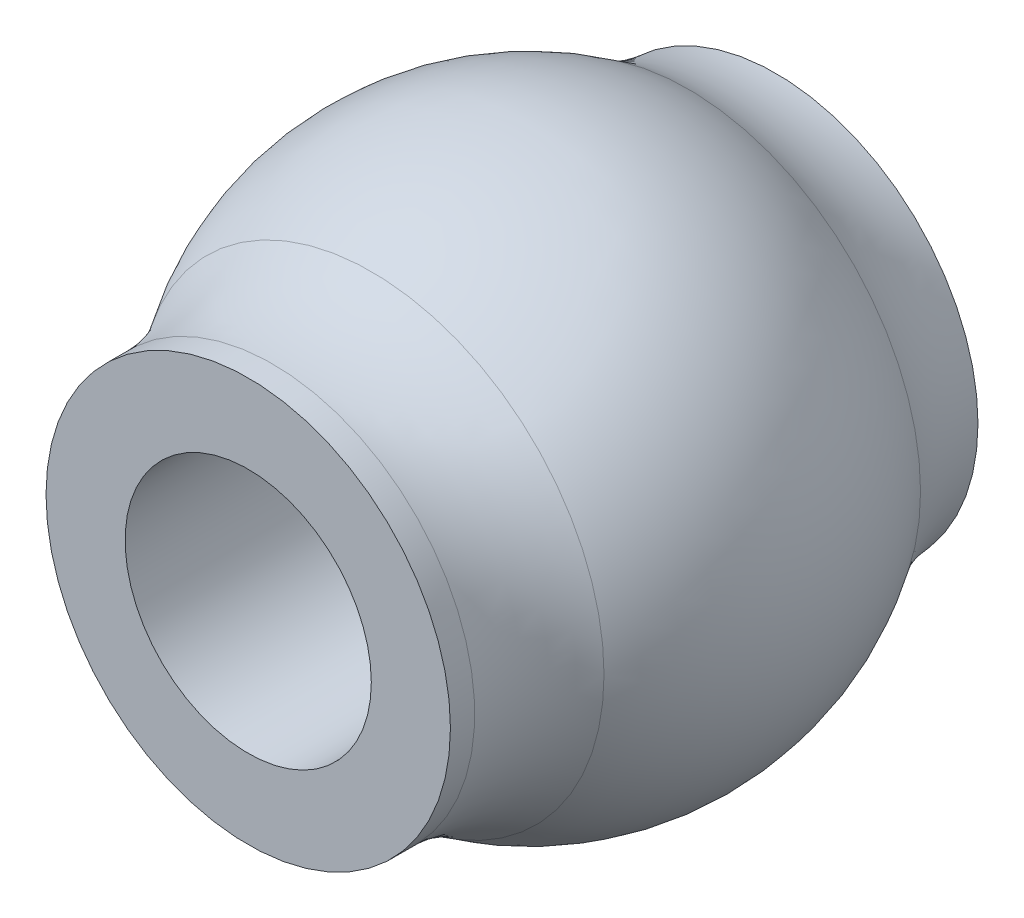
SolidWorks part; units mm, degrees
material "PLA"
ref_plane "Front Plane" through (0, 0, 0) normal (0, 0, 1) x (1, 0, 0)
ref_plane "Top Plane" through (0, 0, 0) normal (0, 1, 0) x (1, 0, 0)
ref_plane "Right Plane" through (0, 0, 0) normal (1, 0, 0) x (0, 0, -1)
sketch "Sketch1" plane through (0, 0, 0) normal (0, 1, 0) x (1, 0, 0)
  line L0 (8.875, 0.2811) -> (6, 0.2811)
  line L1 (6, 0.2811) -> (6, -5.2811)
  line L2 (6, -5.2811) -> (8.875, -5.2811)
  line L3 (6, 0.2811) -> (6, -5.2811) construction
  arc A0 (8.875, -5.2811) -> (8.875, 0.2811) centre (6, -2.5) ccw
revolve "Revolve1" add sketch "Sketch1" angle 360 about L3 reverse direction yes
ref_plane "Plane1" through (0, 0, 2.5) normal (0, 0, 1) x (1, 0, 0)
sketch "Sketch2" plane through (0, 0, -0.2811) normal (0, 0, -1) x (-1, 0, 0)
  circle A0 centre (-6, 0) radius 2.875
extrude "Boss-Extrude1" add sketch "Sketch2" along normal blind 0.7189
sketch "Sketch3" plane through (0, 0, 5.2811) normal (0, 0, 1) x (1, 0, 0)
  circle A0 centre (6, 0) radius 2.875
extrude "Boss-Extrude2" add sketch "Sketch3" along normal blind 1.2189
sketch "Sketch4" plane through (0, 0, -1) normal (0, 0, -1) x (-1, 0, 0)
  circle A0 centre (-6, 0) radius 1.75
extrude "Cut-Extrude1" cut sketch "Sketch4" against normal through all
fillet "Fillet1" radius 2.5 2 edges at (8.875, 0, 5.2811) (3.125, 0, -0.2811) tangent propagation no
